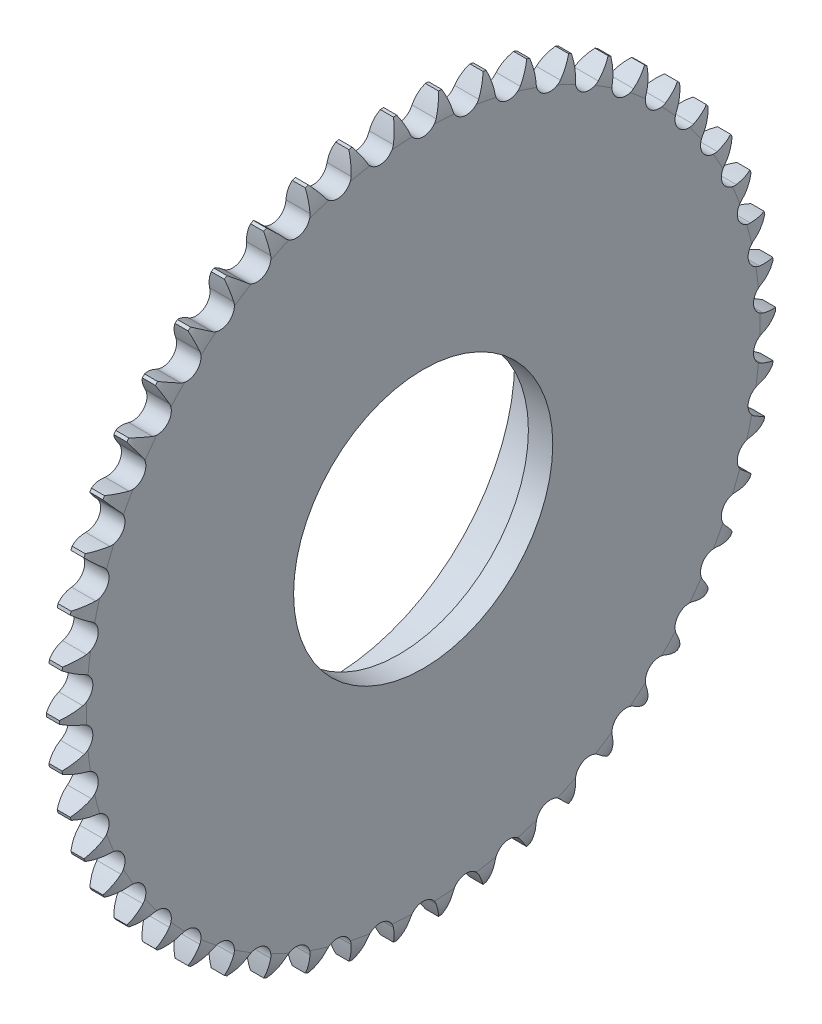
SolidWorks part; units mm, degrees
ref_plane "Plane1" through (0, 0, 0) normal (0, 0, 1) x (1, 0, 0)
ref_plane "Plane2" through (0, 0, 0) normal (0, 1, 0) x (1, 0, 0)
ref_plane "Plane3" through (0, 0, 0) normal (1, 0, 0) x (0, 0, -1)
sketch "Clipboard" plane through (0, 0, 0) normal (0, 1, 0) x (1, 0, 0)
  line L0 (0, 0) -> (10.2043, -12.161)
  line L1 (-15, 0) -> (100, 0) construction
  line L2 (0, 0) -> (-1.3675, 1.5456)
  line L3 (0, 0) -> (-14.8288, 5.6677)
  line L4 (0, 0) -> (1.9926, 2.3747)
  line L5 (0, 0) -> (-23.4238, -8.7364)
  line L6 (0, 0) -> (-7.4026, -4.9946)
  line L7 (-1.3675, 1.5456) -> (14.3658, 20.9747)
  line L8 (-76.2, 38.1) -> (-69.8, 38.1)
  line L9 (-73.5462, 42.5082) -> (-72.9534, 42.6013)
  line L10 (-74, 16.6356) -> (-55.89, 16.6356)
  circle A0 centre (0, 0) radius 5.08
  circle A1 centre (0, 0) radius 60
  circle A2 centre (0, 0) radius 60
  dimension "Num_teeth" = 50
  dimension "Thickness" = 8.93
sketch "BasProSke" plane through (0, 0, 0) normal (0, 1, 0) x (1, 0, 0)
  line L0 (-10, 0) -> (60, 0) construction
  line L1 (0, 0) -> (0, 123.4271)
  line L2 (0, 0) -> (8.93, 0)
  line L3 (8.93, 0) -> (8.93, 123.4271)
  line L4 (6.8662, 131.2543) -> (2.0637, 131.2543)
  arc A0 (0, 123.4271) -> (2.0637, 131.2543) centre (15.875, 123.4271) cw
  arc A1 (8.93, 123.4271) -> (6.8662, 131.2543) centre (-6.945, 123.4271) ccw
  dimension "D1" = 15.875
  dimension "Thickness" = 8.93
  dimension "Diameter" = 262.5085
revolve "Base-Revolve" add sketch "BasProSke" angle 360 about L0
sketch "TooCutSke" plane through (0, 0, 0) normal (1, 0, 0) x (0, 0, -1)
  line L0 (0, 126.4632) -> (4.7932, 124.6328) construction
  line L1 (0, 0) -> (0, 107) construction
  line L2 (0, 126.4632) -> (-10, 126.4632) construction
  line L3 (0, 126.4632) -> (-4.7932, 124.6328) construction
  arc A0 (4.7932, 124.6328) -> (7.9038, 131.517) centre (64.0203, 102.0162) cw
  arc A1 (4.7932, 124.6328) -> (-4.7932, 124.6328) centre (0, 126.4632) cw
  arc A2 (-4.7932, 124.6328) -> (-7.9038, 131.517) centre (-64.0203, 102.0162) ccw
  arc A3 (7.9038, 131.517) -> (-7.9038, 131.517) centre (0, 0) ccw
extrude "ToothCut" cut sketch "TooCutSke" along normal through all
pattern_circular "TeethCuts" count 50 every 7.2 about axis through (-10, 0, 0) along (1, 0, 0) of "ToothCut"
sketch "HubNeaOneSke" plane through (0, 0, 0) normal (-1, 0, 0) x (0, 0, 1)
  circle A0 centre (0, 0) radius 75
  dimension "D1" = 150
extrude "HubNearOne" add sketch "HubNeaOneSke" along normal blind 25
fillet "HubNearOneFillet" radius 0.6 1 edges at (0, 0, -75)
sketch "HubNeaBotSke" plane through (0, 0, 0) normal (-1, 0, 0) x (0, 0, 1)
  circle A0 centre (0, 0) radius 60
  dimension "Diameter" = 120
extrude "HubNearBoth" [suppressed] add sketch "HubNeaBotSke" along normal blind 8.0352
fillet "HubNearBothFillet" [suppressed] radius 0.6
ref_plane "FarPln" through (8.93, 0, 0) normal (1, 0, 0) x (0, 0, -1)
sketch "HubFarSke" plane through (8.93, 0, 0) normal (1, 0, 0) x (0, 0, -1)
  circle A0 centre (0, 0) radius 60
  dimension "Diameter" = 120
extrude "HubFar" [suppressed] add sketch "HubFarSke" along normal blind 8.0352
fillet "HubFarFillet" [suppressed] radius 0.6
sketch "BorSke" plane through (0, 0, 0) normal (1, 0, 0) x (0, 0, -1)
  circle A0 centre (0, 0) radius 47.5
  dimension "Diameter" = 95
extrude "Bore" cut sketch "BorSke" along normal mid plane 50.001
sketch "KeySke" plane through (0, 0, 0) normal (1, 0, 0) x (0, 0, -1)
  line L0 (-14, 0) -> (-14, 53.9)
  line L1 (-14, 53.9) -> (14, 53.9)
  line L2 (14, 53.9) -> (14, 0)
  line L3 (0, 0) -> (0, 34) construction
  line L4 (-14, 0) -> (14, 0)
  dimension "Width" = 28
extrude "Keyway" [suppressed] cut sketch "KeySke" along normal mid plane 50.001
pattern_circular "Keyway2" [suppressed] count 2 every 90 about axis through (-10, 0, 0) along (1, 0, 0) reverse direction yes
sketch "Schizzo2" plane through (-25, 0, 0) normal (-1, 0, 0) x (0, 0, 1)
  circle A0 centre (0, 0) radius 67.5
extrude "Taglio-Estrusione1" cut sketch "Schizzo2" against normal blind 25
equation "' \"Pitch@Clipboard\" = 12.7"
equation "' \"Num_strands@Clipboard\" = 1"
equation "' \"Num_teeth@Clipboard\" = 9"
equation "' \"Hub_dia@Clipboard\" = 50"
equation "' \"Overall_len@Clipboard\" = 3"
equation "' \"Diameter@BorSke\" = 12"
equation "' \"T_dim@Clipboard\" = 1"
equation "' \"Width@KeySke\" = 2"
equation "' \"Dr@Clipboard\" = 8.51"
equation "' \"Face_width@Clipboard\" = 7.2"
equation "' \"Side_radius@Clipboard\" = 12.7"
equation "' \"Side_relief@Clipboard\" = 1.27"
equation "' \"Transv_pitch@Clipboard\" = 13.92"
equation "' \"Show_teeth@Clipboard\" = 9"
equation "' \"Fillet_rad@Clipboard\" = 0.6"
equation "' \"Plate_wid@Clipboard\" = 11.8"
equation "\"Num_teeth@Clipboard\" = int( \"Num_teeth@Clipboard\" )"
equation "\"Num_teeth@Clipboard\" = ((sgn( \"Num_teeth@Clipboard\" - 5.0)+1)*( \"Num_teeth@Clipboard\" - 5.0))/2 +5.0"
equation "\"Num_teeth@Clipboard\" = ((sgn( \"Num_teeth@Clipboard\" - 200.0)-1)*( \"Num_teeth@Clipboard\" - 200.0))/-2 +200.0"
equation "\"MHD@Clipboard\" = \"Pitch@Clipboard\" * (1.0 / tan(3.14159265 / \"Num_teeth@Clipboard\" )) - 1.04 * \"Plate_wid@Clipboard\" - 0.76"
equation "\"Thickness@Clipboard\"  = \"Face_width@Clipboard\" + (\"Num_strands@Clipboard\" - 1) * \"Transv_pitch@Clipboard\""
equation "\"OAL@Clipboard\" = \"Thickness@Clipboard\" + 2 * \"Fillet_rad@Clipboard\" + 1"
equation "\"MHD@Clipboard\" = ((sgn( \"MHD@Clipboard\" - \"Hub_dia@Clipboard\" )-1)*( \"MHD@Clipboard\" - \"Hub_dia@Clipboard\" ))/-2+ \"Hub_dia@Clipboard\""
equation "\"OAL@Clipboard\" = ((sgn( \"OAL@Clipboard\" - \"Overall_len@Clipboard\" )+1)*( \"OAL@Clipboard\" - \"Overall_len@Clipboard\" ))/2 + \"Overall_len@Clipboard\" + 0.0005"
equation "\"Num_teeth@TeethCuts\" = int( \"Show_teeth@Clipboard\" ) + 1"
equation "\"Num_teeth@TeethCuts\" = ((sgn( \"Num_teeth@TeethCuts\" - \"Num_teeth@Clipboard\" )-1)*( \"Num_teeth@TeethCuts\" - \"Num_teeth@Clipboard\" ))/-2+ \"Num_teeth@Clipboard\""
equation "\"Num_teeth@TeethCuts\" = ((sgn( \"Num_teeth@TeethCuts\" - 2.0)+1)*( \"Num_teeth@TeethCuts\" - 2.0))/2 +2.0"
equation "\"Angle@TeethCuts\" = 360.0 / \"Num_teeth@Clipboard\""
equation "\"Seat_radius@TooCutSke\" = ( \"Pitch@Clipboard\" / 2.0) / sin(3.14159265 / \"Num_teeth@Clipboard\" ) - \"Dr@Clipboard\" / 2.0 + \"Dr@Clipboard\" * 0.505"
equation "\"R1@TooCutSke\"  = \"Dr@Clipboard\" * 0.505"
equation "\"X@TooCutSke\" = 140.0 - (90.0 / \"Num_teeth@Clipboard\")"
equation "\"R2@TooCutSke\" = 0.12 * \"Dr@Clipboard\" * ( \"Num_teeth@Clipboard\" + 2.0)"
equation "\"Overcut@TooCutSke\" = 0.5 + 0.625 * \"Pitch@Clipboard\" - 0.5 * \"Dr@Clipboard\"  +  \"Pitch@Clipboard\" / 2.0 / sin(3.14159265 / \"Num_teeth@Clipboard\" )"
equation "\"Diameter@BasProSke\" = 2.0 * ( 0.625 * \"Pitch@Clipboard\" - 0.5 * \"Dr@Clipboard\"  +  \"Pitch@Clipboard\" / 2.0 / sin(3.14159265 / \"Num_teeth@Clipboard\" ))"
equation "\"Thickness@BasProSke\"  = \"Thickness@Clipboard\""
equation "\"G1@BasProSke\" =  \"Side_relief@Clipboard\""
equation "\"G2@BasProSke\" =  \"Side_relief@Clipboard\""
equation "\"D1@BasProSke\" =  \"Side_radius@Clipboard\""
equation "\"Diameter@HubNeaBotSke\" = \"MHD@Clipboard\""
equation "\"Length@HubNearBoth\" = ( \"OAL@Clipboard\" - \"Thickness@BasProSke\" ) / 2.0"
equation "\"D1@HubNearOneFillet\" = \"Fillet_rad@Clipboard\""
equation "\"D1@HubNearBothFillet\" = \"Fillet_rad@Clipboard\""
equation "\"Thickness@FarPln\" = \"Thickness@BasProSke\""
equation "\"Diameter@HubFarSke\" = \"MHD@Clipboard\""
equation "\"Length@HubFar\" = ( \"OAL@Clipboard\" - \"Thickness@BasProSke\" ) / 2.0"
equation "\"D1@HubFarFillet\" = \"Fillet_rad@Clipboard\""
equation "\"D1@Bore\" = \"OAL@Clipboard\" * 2.0"
equation "\"D1@Keyway\" = \"OAL@Clipboard\" * 2.0"
equation "\"Offset@KeySke\" = \"T_dim@Clipboard\" + \"Diameter@BorSke\" / 2.0"
